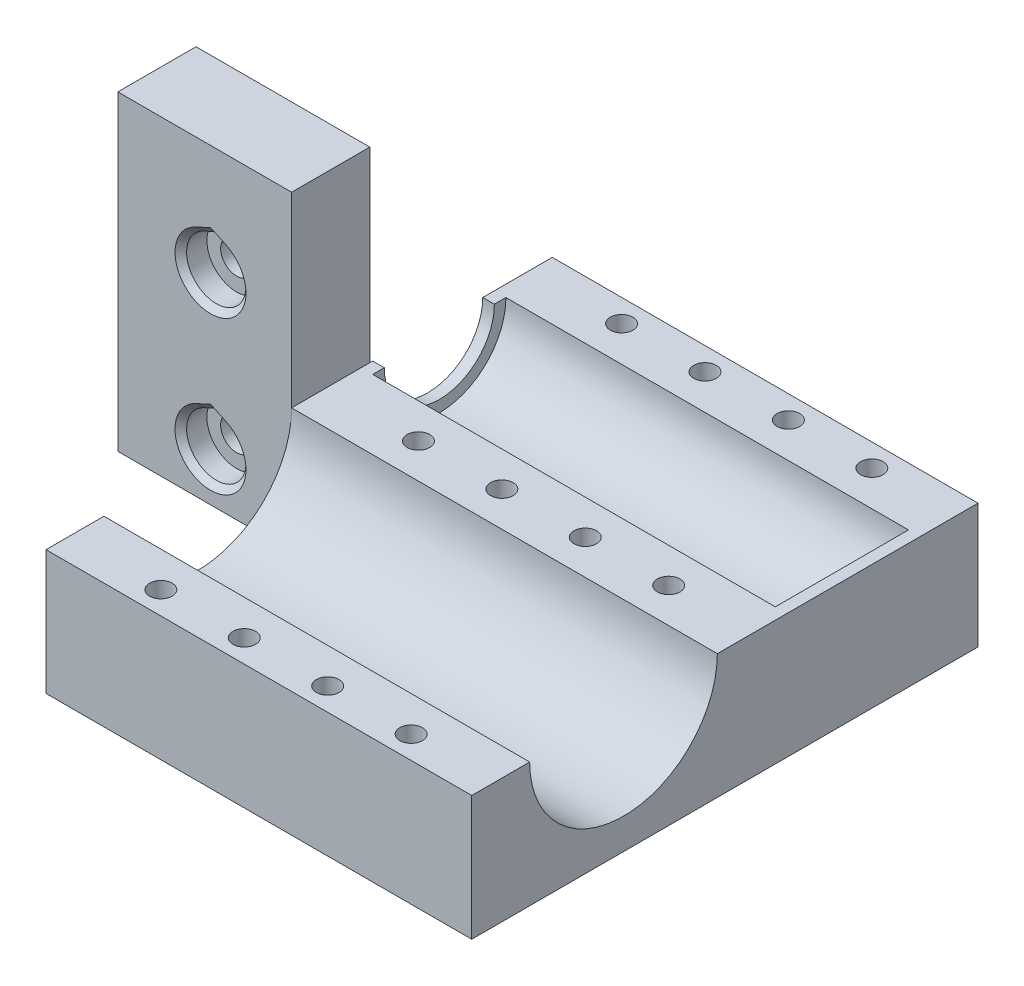
SolidWorks part; units mm, degrees
ref_plane "Front Plane" through (0, 0, 0) normal (0, 0, 1) x (1, 0, 0)
ref_plane "Top Plane" through (0, 0, 0) normal (0, 1, 0) x (1, 0, 0)
ref_plane "Right Plane" through (0, 0, 0) normal (1, 0, 0) x (0, 0, -1)
sketch "Sketch1" plane through (0, 0, 0) normal (1, 0, 0) x (0, 0, -1)
  line L0 (43.7, 42.0261) -> (43.7, 0) construction
  line L1 (0, 0) -> (87.4, 0)
  line L2 (0, 0) -> (0, 21.5)
  line L3 (87.4, 0) -> (87.4, 21.5)
  line L4 (0, 21.5) -> (10, 21.5) construction
  line L6 (42.4, 21.5) -> (54.4, 21.5) construction
  line L7 (42.4, 21.5) -> (54.4, 21.5)
  line L8 (0, 21.5) -> (10, 21.5)
  line L10 (42.4, 21.5) -> (54.4, 21.5)
  line L11 (77.4, 21.5) -> (87.4, 21.5)
  arc A0 (10, 21.5) -> (42.4, 21.5) centre (26.2, 21.5) ccw
  arc A1 (54.4, 21.5) -> (77.4, 21.5) centre (65.9, 21.5) ccw
  point P15 (65.9, 10)
  dimension "D3" = 11.5
  dimension "D4" = 16.2
  dimension "D1" = 10
  dimension "D2" = 12
  dimension "D5" = 10
extrude "Boss-Extrude1" add sketch "Sketch1" along normal blind 73.5 contours L8 L2 L1 L3 L7 region at (0, 8.5131, -45.7668)
sketch "Sketch7" plane through (0, 0, 0) normal (-1, 0, 0) x (0, 0, 1)
  line L0 (0, 0) -> (-87.4, 0) construction
  line L1 (-55.9, 0) -> (-42.4, 0)
  line L2 (-55.9, 0) -> (-55.9, 53.7409)
  line L3 (-55.9, 53.7409) -> (-42.4, 53.7409)
  line L4 (-42.4, 0) -> (-42.4, 53.7409)
  line L5 (-42.4, 21.5) -> (-54.4, 21.5) construction
  line L6 (-42.4, 21.5) -> (-54.4, 21.5) construction
  arc A0 (-77.4, 21.5) -> (-54.4, 21.5) centre (-65.9, 21.5) ccw construction
  arc A1 (-77.4, 21.5) -> (-54.4, 21.5) centre (-65.9, 21.5) ccw construction
  circle A2 centre (-65.9, 21.5) radius 6 construction
  dimension "D1" = 12
  dimension "D2" = 10
extrude "Boss-Extrude2" add sketch "Sketch7" along normal blind 30
sketch "Sketch14" plane through (73.5, 0, 0) normal (1, 0, 0) x (0, 0, -1)
  line L0 (54.4, 21.5) -> (77.4, 21.5)
  arc A0 (54.4, 21.5) -> (77.4, 21.5) centre (65.9, 21.5) ccw construction
  arc A1 (54.4, 21.5) -> (77.4, 21.5) centre (65.9, 21.5) ccw
extrude "Boss-Extrude3" add sketch "Sketch14" against normal blind 2
sketch "Sketch19" plane through (0, 0, 0) normal (-1, 0, 0) x (0, 0, 1)
  line L1 (-75.4, 21.5) -> (-77.4, 21.5)
  line L2 (-56.4, 21.5) -> (-54.4, 21.5)
  arc A5 (-55.9, 15.8211) -> (-54.4, 21.5) centre (-65.9, 21.5) ccw construction
  arc A7 (-77.4, 21.5) -> (-55.9, 15.8211) centre (-65.9, 21.5) ccw construction
  arc A8 (-55.9, 15.8211) -> (-54.4, 21.5) centre (-65.9, 21.5) ccw
  arc A9 (-77.4, 21.5) -> (-55.9, 15.8211) centre (-65.9, 21.5) ccw
  arc A10 (-75.4, 21.5) -> (-57.6391, 16.8087) centre (-65.9, 21.5) ccw
  arc A11 (-57.6391, 16.8087) -> (-56.4, 21.5) centre (-65.9, 21.5) ccw
  dimension "D1" = 2
extrude "Boss-Extrude4" add sketch "Sketch19" against normal blind 2
sketch "Sketch8" plane through (0, 0, -55.9) normal (0, 0, -1) x (-1, 0, 0)
  line L0 (30, 53.7409) -> (0, 53.7409) construction
  line L1 (0, 53.7409) -> (0, 21.5) construction
  line L2 (30, 53.7409) -> (0, 53.7409) construction
  line L3 (0, 53.7409) -> (0, 21.5) construction
  line L5 (-2, 21.5) -> (0, 21.5) construction
  line L6 (12.485, 36.9951) -> (14, 37.9951)
  line L7 (14, 37.9951) -> (15.515, 36.9951)
  line L8 (12.485, 36.9951) -> (15.515, 36.9951) construction
  line L9 (14, 11.5951) -> (12.485, 10.5951)
  line L10 (14, 11.5951) -> (15.515, 10.5951)
  line L11 (15.515, 10.5951) -> (12.485, 10.5951) construction
  line L12 (3.5, 21.5) -> (45.8321, 21.5) construction
  line L14 (-2, 21.5) -> (-2, 10) construction
  line L15 (-2, 21.5) -> (-2, 10) construction
  line L16 (-2, 21.5) -> (0, 21.5) construction
  arc A0 (12.485, 36.9951) -> (15.515, 36.9951) centre (14, 34.7) ccw
  arc A1 (12.485, 10.5951) -> (15.515, 10.5951) centre (14, 8.3) ccw
  dimension "D3" = 5.5
  dimension "D2" = 14
  dimension "D5" = 1
  dimension "D6" = 1
  dimension "D1" = 13.2
  dimension "D4" = 13.2
extrude "Cut-Extrude1" cut sketch "Sketch8" against normal up to surface (13.5 mm away) up to face at (-12, 25.7964, -42.4)
sketch "Sketch9" plane through (0, 0, -55.9) normal (0, 0, -1) x (-1, 0, 0)
  line L0 (11.8438, 39.3493) -> (14, 40.3493)
  line L1 (14, 40.3493) -> (16.1562, 39.3493)
  line L2 (11.8438, 39.3493) -> (16.1562, 39.3493) construction
  line L3 (11.8438, 12.9493) -> (14, 13.9493)
  line L4 (14, 13.9493) -> (16.1562, 12.9493)
  line L5 (11.8438, 12.9493) -> (16.1562, 12.9493) construction
  arc A0 (11.8438, 39.3493) -> (16.1562, 39.3493) centre (14, 34.7) ccw
  arc A1 (11.8438, 12.9493) -> (16.1562, 12.9493) centre (14, 8.3) ccw
  dimension "D1" = 10.25
  dimension "D2" = 1
  dimension "D3" = 1
extrude "Cut-Extrude2" cut sketch "Sketch9" against normal blind 4.5
sketch "Sketch10" plane through (0, 0, -42.4) normal (0, 0, 1) x (1, 0, 0)
  line L0 (-16.1562, 39.3493) -> (-14, 40.3493)
  line L1 (-14, 40.3493) -> (-11.8438, 39.3493)
  line L2 (-16.1562, 39.3493) -> (-11.8438, 39.3493) construction
  line L3 (-16.1562, 12.9493) -> (-14, 13.9493)
  line L4 (-14, 13.9493) -> (-11.8438, 12.9493)
  line L5 (-16.1562, 12.9493) -> (-11.8438, 12.9493) construction
  arc A0 (-16.1562, 39.3493) -> (-11.8438, 39.3493) centre (-14, 34.7) ccw
  arc A1 (-16.1562, 12.9493) -> (-11.8438, 12.9493) centre (-14, 8.3) ccw
  dimension "D1" = 10.25
  dimension "D2" = 1
  dimension "D3" = 1
extrude "Cut-Extrude8" cut sketch "Sketch10" against normal blind 4.5
sketch "Sketch22" plane through (0, 21.5, 0) normal (0, 1, 0) x (1, 0, 0)
  line L0 (73.5, 42.4) -> (0, 42.4) construction
  line L1 (71.5, 54.4) -> (2, 54.4) construction
  line L2 (73.5, 42.4) -> (0, 42.4) construction
  line L3 (71.5, 54.4) -> (2, 54.4) construction
  line L4 (36.75, 54.4) -> (36.75, 42.4) construction
  line L5 (36.75, 48.4) -> (1.5, 48.4) construction
  line L6 (36.75, 48.4) -> (73.5, 48.4) construction
  line L7 (73.5, 42.4) -> (73.5, 87.4) construction
  line L8 (73.5, 10) -> (73.5, 42.4) construction
  line L9 (71.5, 77.4) -> (71.5, 54.4) construction
  line L10 (73.5, 10) -> (73.5, 42.4) construction
  line L11 (71.5, 77.4) -> (71.5, 54.4) construction
  line L12 (71.5, 65.9) -> (-4.6102, 65.9) construction
  line L13 (73.5, 26.2) -> (-9.4707, 26.2) construction
  line L14 (6.2217, 83.47) -> (64.0919, 83.47) construction
  line L16 (10.6744, 3.93) -> (59.5979, 3.93) construction
  line L18 (73.5, 87.4) -> (0, 87.4) construction
  line L21 (73.5, 0) -> (0, 0) construction
  circle A0 centre (15.9, 48.4) radius 1.95
  circle A1 centre (30.3, 48.4) radius 1.95
  circle A2 centre (44.7, 48.4) radius 1.95
  circle A3 centre (59.1, 48.4) radius 1.95
  circle A5 centre (59.1, 83.47) radius 1.95
  circle A8 centre (30.3, 83.47) radius 1.95
  circle A9 centre (15.9, 83.47) radius 1.95
  circle A10 centre (44.7, 3.93) radius 1.95
  circle A11 centre (59.1, 3.93) radius 1.95
  circle A14 centre (15.9, 3.93) radius 1.95
  circle A15 centre (44.7, 83.47) radius 1.95
  circle A16 centre (30.3, 3.93) radius 1.95
  dimension "D1" = 3.9
  dimension "D2" = 72
  dimension "D3" = 14.4
  dimension "D4" = 14.4
  dimension "D5" = 14.4
  dimension "D6" = 14.4
  dimension "D7" = 3.93
  dimension "D8" = 3.93
extrude "Cut-Extrude9" cut sketch "Sketch22" against normal up to surface (21.5 mm away) up to face at (10.875, 0, -46.425)
sketch "Sketch24" plane through (0, 0, 0) normal (0, -1, 0) x (1, 0, 0)
  line L1 (18.781, -4.9313) -> (18.2076, -1.9357)
  line L2 (18.2076, -1.9357) -> (15.3267, -0.9344)
  line L3 (15.3267, -0.9344) -> (13.019, -2.9287)
  line L4 (13.019, -2.9287) -> (13.5924, -5.9243)
  line L5 (13.5924, -5.9243) -> (16.4733, -6.9256)
  line L6 (16.4733, -6.9256) -> (18.781, -4.9313)
  line L7 (33.1764, -4.9442) -> (32.6165, -1.946)
  line L8 (32.6165, -1.946) -> (29.7401, -0.9318)
  line L9 (29.7401, -0.9318) -> (27.4236, -2.9158)
  line L10 (27.4236, -2.9158) -> (27.9835, -5.914)
  line L11 (27.9835, -5.914) -> (30.8599, -6.9282)
  line L12 (30.8599, -6.9282) -> (33.1764, -4.9442)
  line L13 (47.5773, -4.9416) -> (47.0148, -1.944)
  line L14 (47.0148, -1.944) -> (44.1374, -0.9323)
  line L15 (44.1374, -0.9323) -> (41.8227, -2.9184)
  line L16 (41.8227, -2.9184) -> (42.3852, -5.916)
  line L17 (42.3852, -5.916) -> (45.2626, -6.9277)
  line L18 (45.2626, -6.9277) -> (47.5773, -4.9416)
  line L19 (61.978, -4.9397) -> (61.4134, -1.9424)
  line L20 (61.4134, -1.9424) -> (58.5354, -0.9327)
  line L21 (58.5354, -0.9327) -> (56.222, -2.9203)
  line L22 (56.222, -2.9203) -> (56.7866, -5.9176)
  line L23 (56.7866, -5.9176) -> (59.6646, -6.9273)
  line L24 (59.6646, -6.9273) -> (61.978, -4.9397)
  line L25 (62.0926, -48.9887) -> (61.1062, -46.1027)
  line L26 (61.1062, -46.1027) -> (58.1135, -45.5139)
  line L27 (58.1135, -45.5139) -> (56.1074, -47.8113)
  line L28 (56.1074, -47.8113) -> (57.0938, -50.6973)
  line L29 (57.0938, -50.6973) -> (60.0865, -51.2861)
  line L30 (60.0865, -51.2861) -> (62.0926, -48.9887)
  line L31 (47.6946, -48.9785) -> (46.6983, -46.0959)
  line L32 (46.6983, -46.0959) -> (43.7037, -45.5173)
  line L33 (43.7037, -45.5173) -> (41.7054, -47.8215)
  line L34 (41.7054, -47.8215) -> (42.7017, -50.7041)
  line L35 (42.7017, -50.7041) -> (45.6963, -51.2827)
  line L36 (45.6963, -51.2827) -> (47.6946, -48.9785)
  line L37 (33.2885, -49.0095) -> (32.3221, -46.1167)
  line L38 (32.3221, -46.1167) -> (29.3336, -45.5071)
  line L39 (29.3336, -45.5071) -> (27.3115, -47.7905)
  line L40 (27.3115, -47.7905) -> (28.2779, -50.6833)
  line L41 (28.2779, -50.6833) -> (31.2664, -51.2929)
  line L42 (31.2664, -51.2929) -> (33.2885, -49.0095)
  line L43 (18.884, -49.0308) -> (17.9384, -46.1312)
  line L44 (17.9384, -46.1312) -> (14.9543, -45.5003)
  line L45 (14.9543, -45.5003) -> (12.916, -47.7692)
  line L46 (12.916, -47.7692) -> (13.8616, -50.6688)
  line L47 (13.8616, -50.6688) -> (16.8457, -51.2997)
  line L48 (16.8457, -51.2997) -> (18.884, -49.0308)
  line L49 (15.7488, -86.5162) -> (18.4625, -85.1241)
  line L50 (18.4625, -85.1241) -> (18.6137, -82.0779)
  line L51 (18.6137, -82.0779) -> (16.0512, -80.4238)
  line L52 (16.0512, -80.4238) -> (13.3375, -81.8159)
  line L53 (13.3375, -81.8159) -> (13.1863, -84.8621)
  line L54 (13.1863, -84.8621) -> (15.7488, -86.5162)
  line L55 (30.1491, -86.5163) -> (32.8627, -85.1238)
  line L56 (32.8627, -85.1238) -> (33.0136, -82.0776)
  line L57 (33.0136, -82.0776) -> (30.4509, -80.4237)
  line L58 (30.4509, -80.4237) -> (27.7373, -81.8162)
  line L59 (27.7373, -81.8162) -> (27.5864, -84.8624)
  line L60 (27.5864, -84.8624) -> (30.1491, -86.5163)
  line L61 (44.5485, -86.5162) -> (47.2624, -85.1243)
  line L62 (47.2624, -85.1243) -> (47.4139, -82.0781)
  line L63 (47.4139, -82.0781) -> (44.8515, -80.4238)
  line L64 (44.8515, -80.4238) -> (42.1376, -81.8157)
  line L65 (42.1376, -81.8157) -> (41.9861, -84.8619)
  line L66 (41.9861, -84.8619) -> (44.5485, -86.5162)
  line L67 (58.9488, -86.5162) -> (61.6625, -85.1241)
  line L68 (61.6625, -85.1241) -> (61.8137, -82.0779)
  line L69 (61.8137, -82.0779) -> (59.2512, -80.4238)
  line L70 (59.2512, -80.4238) -> (56.5375, -81.8159)
  line L71 (56.5375, -81.8159) -> (56.3863, -84.8621)
  line L72 (56.3863, -84.8621) -> (58.9488, -86.5162)
  circle A0 centre (15.9, -3.93) radius 2.6414 construction
  circle A1 centre (30.3, -3.93) radius 2.6414 construction
  circle A2 centre (44.7, -3.93) radius 2.6414 construction
  circle A3 centre (59.1, -3.93) radius 2.6414 construction
  circle A4 centre (59.1, -48.4) radius 2.6414 construction
  circle A5 centre (44.7, -48.4) radius 2.6414 construction
  circle A6 centre (30.3, -48.4) radius 2.6414 construction
  circle A7 centre (15.9, -48.4) radius 2.6414 construction
  circle A8 centre (15.9, -83.47) radius 2.6414 construction
  circle A9 centre (30.3, -83.47) radius 2.6414 construction
  circle A10 centre (44.7, -83.47) radius 2.6414 construction
  circle A11 centre (59.1, -83.47) radius 2.6414 construction
  dimension "D1" = 6.1
extrude "Cut-Extrude10" cut sketch "Sketch24" against normal blind 3
chamfer "Chamfer1" distance 1 angle 45 12 edges at (-15.0781, 13.4493, -42.4) (-12.9219, 13.4493, -42.4) (-14, 3.175, -42.4) (-15.0781, 39.8493, -42.4) (-12.9219, 39.8493, -42.4) (-14, 29.575, -42.4) (-12.9219, 13.4493, -55.9) (-15.0781, 13.4493, -55.9) (-14, 3.175, -55.9) (-12.9219, 39.8493, -55.9) (-15.0781, 39.8493, -55.9) (-14, 29.575, -55.9)
equation "\"MotorDIA\"= 22'ME 405 Motor Diameter"
equation "\"SyringeDIA\"= 31.4'60ml Syringe Diameter"
equation "\"MotorShaftDIA\"= 6'Motor Shaft Dia"
equation "\"MotorKeyway\"= 1'ME 405 Motor Shaft Keyway Depth"
equation "\"MotorLength\"= 67.5'ME 405 Motor Length Excluding Shaft"
equation "\"SyringeLength\"= 117.3'60ml Syringe Length Excluding Nozzle"
equation "\"3Dtol\"= .5'Sizing Tolerance for 3D printed parts"
equation "\"ChamberDIA\"= 100 - 4'Buoyancy Chamber inner Diameter"
equation "\"ChamberThk\"= 2mm'Buoyancy Chamber Wall Thickness"
equation "\"D4@Sketch1\"=\"SyringeDIA\"/2+\"3Dtol\""
equation "\"D3@Sketch1\"=\"MotorDIA\"/2+\"3Dtol\""
equation "\"D1@Boss-Extrude1\"=\"MotorLength\"+4*\"3Dtol\"+4mm"
equation "\"D3@Sketch22\"=\"D2@Sketch22\"/5"
equation "\"D4@Sketch22\"=\"D3@Sketch22\""
equation "\"D5@Sketch22\"=\"D3@Sketch22\""
equation "\"D6@Sketch22\"=\"D3@Sketch22\""
equation "\"D4@Sketch8\"=\"D1@Sketch8\""
